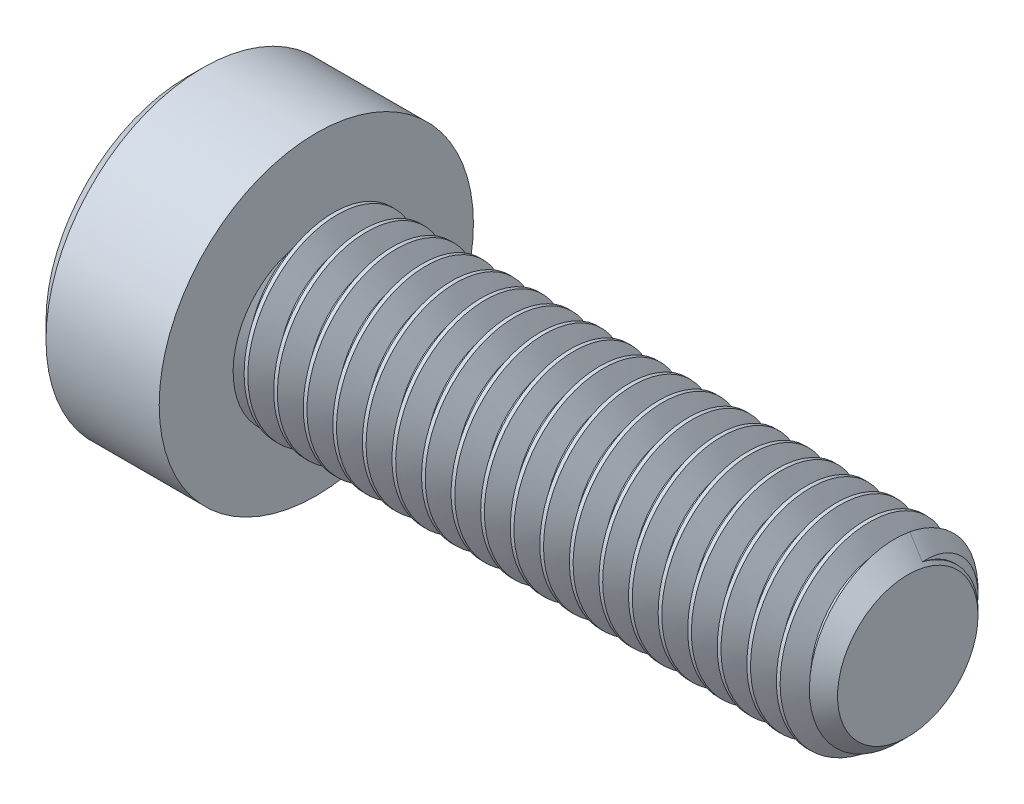
SolidWorks part; units mm, degrees
ref_plane "Front Plane" through (0, 0, 0) normal (0, 0, 1) x (1, 0, 0)
ref_plane "Top Plane" through (0, 0, 0) normal (0, 1, 0) x (1, 0, 0)
ref_plane "Right Plane" through (0, 0, 0) normal (1, 0, 0) x (0, 0, -1)
sketch "Sketch1" plane through (0, 0, 0) normal (0, 0, 1) x (1, 0, 0)
  line L0 (8, 0) -> (-8, 0) construction
  line L1 (8, 2.5) -> (8, -2.5) construction
  line L2 (-8, 4.25) -> (-8, -4.25) construction
  line L3 (-8, 4.25) -> (-11.0625, 4.25) construction
  line L4 (-11.0625, 4.25) -> (-11.5, 3.8125) construction
  line L5 (-11.5, 3.8125) -> (-11.5, -3.8125) construction
  line L6 (-11.5, -3.8125) -> (-11.0625, -4.25) construction
  line L7 (-11.0625, -4.25) -> (-8, -4.25) construction
  point P7 (-8.68, 0)
  point P12 (4.8, -2.5)
  dimension "D1" = 45
  dimension "Dec." = 5
  dimension "Length" = 16
  dimension "Head Dia" = 8.5
  dimension "Head Height" = 3.5
  dimension "Hex Depth" = 2.82
  dimension "Chamfer" = 0.4375
  dimension "D2" = 3.2
ref_plane "Plane1" through (8, 0, 0) normal (1, 0, 0) x (0, 0, -1)
ref_plane "Plane2" through (-11.5, 0, 0) normal (1, 0, 0) x (0, 0, -1)
sketch "Sketch2" plane through (8, 0, 0) normal (1, 0, 0) x (0, 0, -1)
  circle A0 centre (0, 0) radius 2.5
extrude "Boss-Extrude1" add sketch "Sketch2" against normal up to vertex (16 mm away) up to point (-8, 0, 0)
sketch "Sketch3" plane through (8, 0, 0) normal (1, 0, 0) x (0, 0, -1)
  circle A0 centre (0, 0) radius 2.5 construction
  circle A1 centre (0, 0) radius 2.5
curve "Helix/Spiral1" pitch 0.8 height 16.8 radius 2.5 centre (8, 0, 0) axis (-1, 0, 0) start towards (0, 1, 0) parameters "Pitch"=0.8
chamfer "Chamfer1" distance 0.6 angle 45 1 edges at (8, 0, -2.5)
sketch "Sketch5" plane through (0, 0, 0) normal (0, 0, 1) x (1, 0, 0)
  line L0 (7.65, 2.5) -> (8.35, 2.5)
  line L1 (8.35, 2.5) -> (8.05, 1.9804)
  line L2 (8.05, 1.9804) -> (7.95, 1.9804)
  line L3 (7.95, 1.9804) -> (7.65, 2.5)
  line L4 (8, 1.9804) -> (8, 2.5) construction
  line L5 (7.8, 2.2402) -> (8.2, 2.2402) construction
  dimension "D1" = 60
  dimension "D2" = 0.4
  dimension "D3" = 0.1
sweep "Cut-Sweep1" cut profiles "Sketch5" path "Helix/Spiral1" align with end faces yes
sketch "Sketch4" plane through (-11.5, 0, 0) normal (1, 0, 0) x (0, 0, -1)
  line L0 (-4.25, 0.7937) -> (4.25, 0.7937) construction
  line L1 (0, 1.7321) -> (-1.5, 0.866)
  line L2 (-1.5, 0.866) -> (-1.5, -0.866)
  line L3 (-1.5, -0.866) -> (0, -1.7321)
  line L4 (0, -1.7321) -> (1.5, -0.866)
  line L5 (1.5, -0.866) -> (1.5, 0.866)
  line L6 (1.5, 0.866) -> (0, 1.7321)
  line L7 (0, 0) -> (0, 0.7937) construction
  circle A0 centre (0, 0) radius 1.5 construction
  dimension "Hex Size" = 3
  dimension "D1" = 8.5
  dimension "D2" = 0.7937
sketch "Sketch6" plane through (0, 0, 0) normal (0, 0, 1) x (1, 0, 0)
  line L0 (-11.0625, 4.25) -> (-11.5, 3.8125) construction
  line L1 (-8, 4.25) -> (-11.0625, 4.25) construction
  line L2 (-8, 4.25) -> (-8, -4.25) construction
  line L3 (-11.5, 3.8125) -> (-11.5, -3.8125) construction
  line L4 (-11.0625, 4.25) -> (-11.5, 3.8125)
  line L5 (-8, 4.25) -> (-11.0625, 4.25)
  line L6 (-8, 4.25) -> (-8, 0)
  line L7 (-11.5, 3.8125) -> (-11.5, 0)
  line L8 (-8, 0) -> (-11.5, 0) construction
  line L9 (-8, 0) -> (-11.5, 0)
revolve "Revolve1" add sketch "Sketch6" angle 360 about L8
extrude "Cut-Extrude1" cut sketch "Sketch4" along normal up to vertex (2.82 mm away) up to point (-8.68, 0, 0)
sketch "Sketch8" plane through (-11.5, 0, 0) normal (-1, 0, 0) x (0, 0, 1)
  circle A1 centre (0, 0) radius 1.7321
extrude "Cut-Extrude2" cut sketch "Sketch8" against normal through all draft 45
equation "\"D3@Helix/Spiral1\" = \"Length@Sketch1\"+\"Pitch@Helix/Spiral1\""
equation "\"D3@Sketch5\" = \"Pitch@Helix/Spiral1\"*.125"
equation "\"D2@Sketch5\" = \"Pitch@Helix/Spiral1\"*.50"
equation "\"D1@Chamfer1\" = \"Pitch@Helix/Spiral1\"*.75"
equation "\"D2@Sketch1\" = \"Pitch@Helix/Spiral1\"*4"
equation "\"D1@Sketch4\" = \"Head Dia@Sketch1\""
equation "\"Chamfer@Sketch1\" = \"Head Height@Sketch1\"/8"
